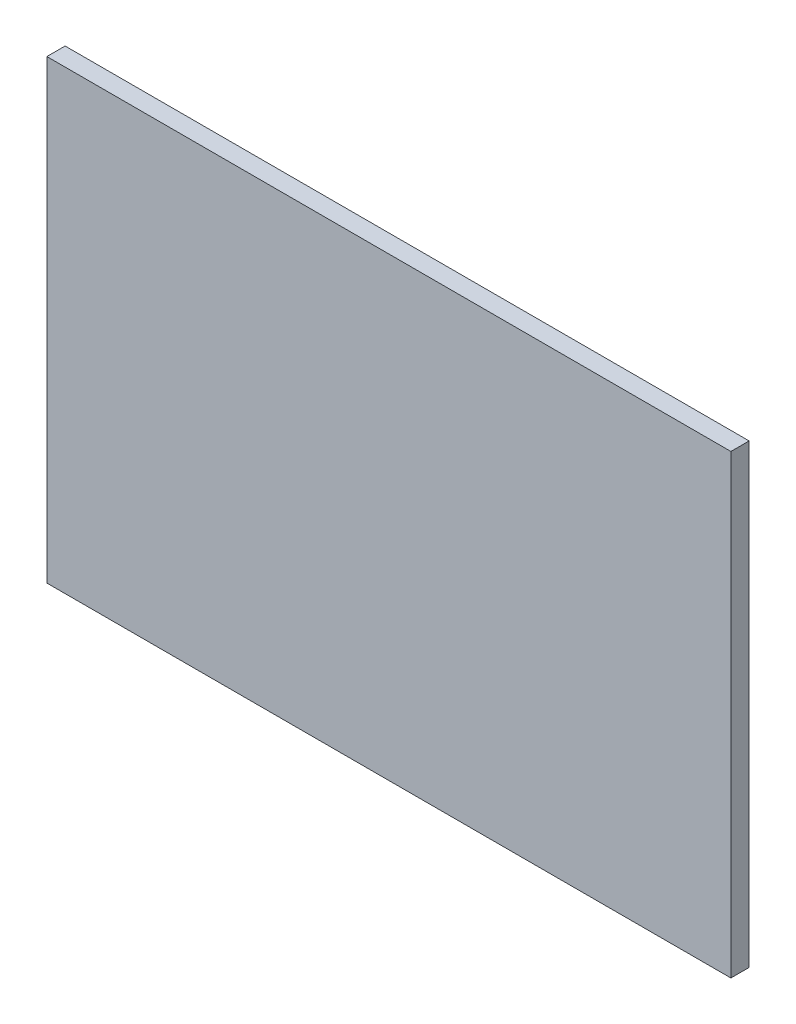
SolidWorks part; units mm, degrees
material "Glass"
ref_plane "Front Plane" through (0, 0, 0) normal (0, 0, 1) x (1, 0, 0)
ref_plane "Top Plane" through (0, 0, 0) normal (0, 1, 0) x (1, 0, 0)
ref_plane "Right Plane" through (0, 0, 0) normal (1, 0, 0) x (0, 0, -1)
sketch "Sketch1" plane through (0, 0, 0) normal (0, 1, 0) x (1, 0, 0)
  line L0 (0, -21) -> (0, 21) construction
  line L2 (-75, -21) -> (75, -21)
  line L3 (-75, -21) -> (-75, -25)
  line L4 (-75, -25) -> (75, -25)
  line L5 (75, -21) -> (75, -25)
  line L6 (-75, 21) -> (75, 21)
  line L7 (-75, 21) -> (-75, 25)
  line L8 (-75, 25) -> (75, 25)
  line L9 (75, 21) -> (75, 25)
  point P4 (0, 0)
  dimension "D1" = 42
  dimension "D2" = 150
  dimension "D3" = 4
extrude "Boss-Extrude1" add sketch "Sketch1" along normal blind 100 contours L5 L2 L3 L4 region at (0, 0, 23)
equation "\"glass_width\"= 150"
equation "\"glass_height\"= 100"
equation "\"glass_thickness\"= 4"
equation "\"brood_space\"= 42"
